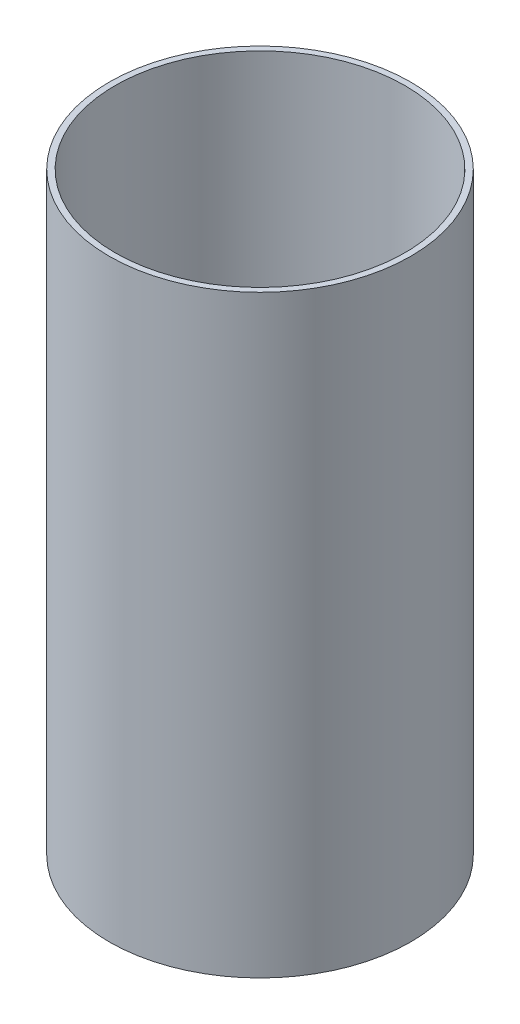
SolidWorks part; units mm, degrees
material "A-Glass Fiber"
ref_plane "Front Plane" through (0, 0, 0) normal (0, 0, 1) x (1, 0, 0)
ref_plane "Top Plane" through (0, 0, 0) normal (0, 1, 0) x (1, 0, 0)
ref_plane "Right Plane" through (0, 0, 0) normal (1, 0, 0) x (0, 0, -1)
sketch "Sketch1" plane through (0, 0, 0) normal (0, 1, 0) x (1, 0, 0)
  circle A0 centre (0, 0) radius 76.2
  circle A1 centre (0, 0) radius 73.2
  dimension "D1" = 152.4
  dimension "D2" = 3
extrude "Boss-Extrude1" add sketch "Sketch1" along normal blind 150 and the other way blind 150
ref_plane "Plane1" through (0, 25, 0) normal (0, 1, 0) x (1, 0, 0)
